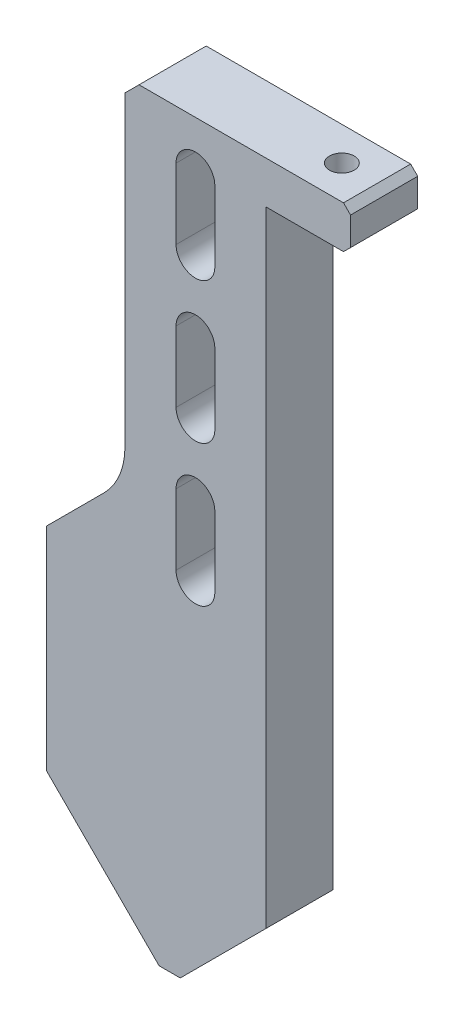
SolidWorks part; units mm, degrees
material "Plain Carbon Steel"
ref_plane "Front Plane" through (0, 0, 0) normal (0, 0, 1) x (1, 0, 0)
ref_plane "Top Plane" through (0, 0, 0) normal (0, 1, 0) x (1, 0, 0)
ref_plane "Right Plane" through (0, 0, 0) normal (1, 0, 0) x (0, 0, -1)
sketch "Sketch1" plane through (0, 0, 0) normal (0, 0, 1) x (1, 0, 0)
  line L0 (-191.4038, 11.3962) -> (-207.4038, 27.3962) construction
  line L1 (-207.4038, 27.3962) -> (-207.4038, 57.3962) construction
  line L2 (-196.2477, 68.5523) -> (-207.4038, 57.3962) construction
  line L3 (-196.2477, 118.1924) -> (-196.2477, 68.5523) construction
  line L4 (-164.2477, 118.1924) -> (-196.2477, 118.1924) construction
  line L5 (-164.2477, 112.1924) -> (-164.2477, 118.1924) construction
  line L6 (-176.2477, 112.1924) -> (-164.2477, 112.1924) construction
  line L7 (-176.2477, 112.1924) -> (-176.2477, 23.5523) construction
  line L8 (-176.2477, 23.5523) -> (-188.4038, 11.3962) construction
  line L9 (-191.4038, 11.3962) -> (-188.4038, 11.3962) construction
  line L10 (-191.4038, 11.3962) -> (-207.4038, 27.3962)
  line L11 (-207.4038, 27.3962) -> (-207.4038, 57.3962)
  line L12 (-196.2477, 68.5523) -> (-207.4038, 57.3962)
  line L13 (-196.2477, 118.1924) -> (-196.2477, 68.5523)
  line L14 (-164.2477, 118.1924) -> (-196.2477, 118.1924)
  line L15 (-164.2477, 112.1924) -> (-164.2477, 118.1924)
  line L16 (-176.2477, 112.1924) -> (-164.2477, 112.1924)
  line L17 (-176.2477, 112.1924) -> (-176.2477, 23.5523)
  line L18 (-176.2477, 23.5523) -> (-188.4038, 11.3962)
  line L19 (-191.4038, 11.3962) -> (-188.4038, 11.3962)
  line L20 (-168.7477, 118.1924) -> (-168.7477, 107.1924) construction
  line L21 (-170.2477, 118.1924) -> (-170.2477, 107.1924) construction
  line L22 (-171.7477, 118.1924) -> (-171.7477, 107.1924) construction
  line L23 (-168.7477, 118.1924) -> (-168.7477, 107.1924) construction
  line L24 (-170.2477, 118.1924) -> (-170.2477, 107.1924) construction
  line L25 (-171.7477, 118.1924) -> (-171.7477, 107.1924) construction
  line L26 (-183.4977, 61.1924) -> (-183.4977, 71.1924) construction
  line L27 (-188.9977, 61.1924) -> (-188.9977, 71.1924) construction
  line L28 (-183.4977, 81.1924) -> (-183.4977, 91.1924) construction
  line L29 (-188.9977, 81.1924) -> (-188.9977, 91.1924) construction
  line L30 (-183.4977, 101.1924) -> (-183.4977, 111.1924) construction
  line L31 (-188.9977, 101.1924) -> (-188.9977, 111.1924) construction
  line L32 (-183.4977, 61.1924) -> (-183.4977, 71.1924)
  line L33 (-188.9977, 61.1924) -> (-188.9977, 71.1924)
  line L34 (-183.4977, 81.1924) -> (-183.4977, 91.1924)
  line L35 (-188.9977, 81.1924) -> (-188.9977, 91.1924)
  line L36 (-183.4977, 101.1924) -> (-183.4977, 111.1924)
  line L37 (-188.9977, 101.1924) -> (-188.9977, 111.1924)
  arc A0 (-183.4977, 71.1924) -> (-188.9977, 71.1924) centre (-186.2477, 71.1924) ccw construction
  arc A1 (-188.9977, 61.1924) -> (-183.4977, 61.1924) centre (-186.2477, 61.1924) ccw construction
  arc A2 (-183.4977, 91.1924) -> (-188.9977, 91.1924) centre (-186.2477, 91.1924) ccw construction
  arc A3 (-188.9977, 81.1924) -> (-183.4977, 81.1924) centre (-186.2477, 81.1924) ccw construction
  arc A4 (-183.4977, 111.1924) -> (-188.9977, 111.1924) centre (-186.2477, 111.1924) ccw construction
  arc A5 (-188.9977, 101.1924) -> (-183.4977, 101.1924) centre (-186.2477, 101.1924) ccw construction
  arc A6 (-183.4977, 71.1924) -> (-188.9977, 71.1924) centre (-186.2477, 71.1924) ccw
  arc A7 (-188.9977, 61.1924) -> (-183.4977, 61.1924) centre (-186.2477, 61.1924) ccw
  arc A8 (-183.4977, 91.1924) -> (-188.9977, 91.1924) centre (-186.2477, 91.1924) ccw
  arc A9 (-188.9977, 81.1924) -> (-183.4977, 81.1924) centre (-186.2477, 81.1924) ccw
  arc A10 (-183.4977, 111.1924) -> (-188.9977, 111.1924) centre (-186.2477, 111.1924) ccw
  arc A11 (-188.9977, 101.1924) -> (-183.4977, 101.1924) centre (-186.2477, 101.1924) ccw
extrude "Boss-Extrude1" add sketch "Sketch1" along normal blind 4.7625 and the other way blind 4.7625
sketch "Sketch2" plane through (0, 118.1924, 0) normal (0, 1, 0) x (-1, 0, 0)
  circle A0 centre (170.2477, 0) radius 1.75
  dimension "D1" = 3.5
extrude "Cut-Extrude1" cut sketch "Sketch2" against normal through all
fillet "Fillet1" radius 10 1 edges at (-196.2477, 68.5523, 0)
chamfer "Chamfer1" distance 2 angle 45 1 edges at (-196.2477, 118.1924, 0)
chamfer "Chamfer2" distance 1 angle 45 2 edges at (-164.2477, 118.1924, 0) (-164.2477, 112.1924, 0)
